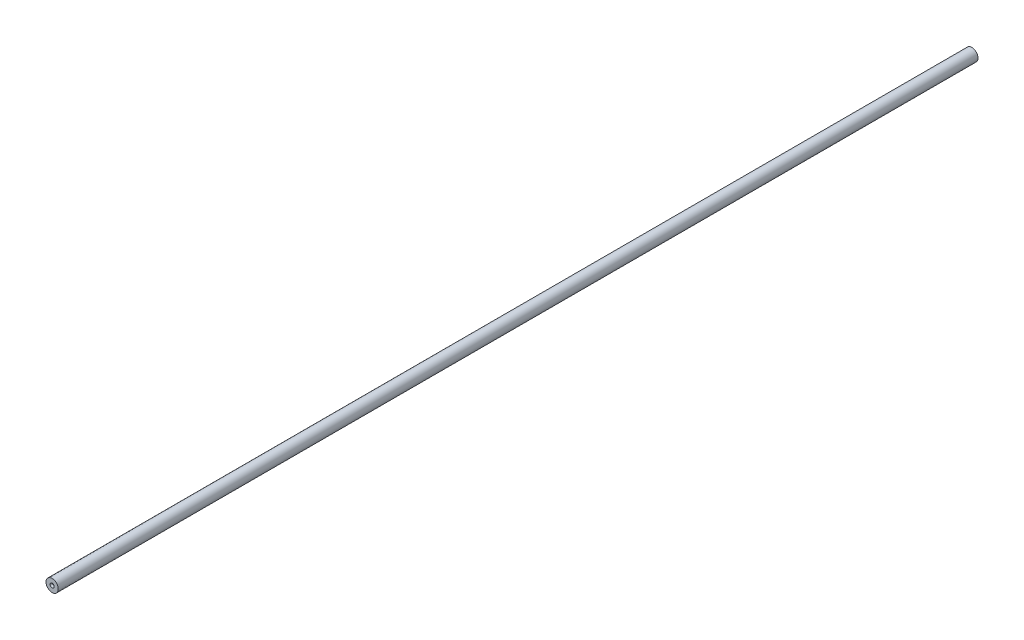
SolidWorks part; units mm, degrees
ref_plane "Front Plane" through (0, 0, 0) normal (0, 0, 1) x (1, 0, 0)
ref_plane "Top Plane" through (0, 0, 0) normal (0, 1, 0) x (1, 0, 0)
ref_plane "Right Plane" through (0, 0, 0) normal (1, 0, 0) x (0, 0, -1)
sketch "Sketch1" plane through (0, 0, 0) normal (0, 0, 1) x (1, 0, 0)
  circle A0 centre (0, 0) radius 8
  dimension "D1" = 16
extrude "Boss-Extrude1" add sketch "Sketch1" along normal mid plane 1200
cosmetic thread "Cosmetic Thread1" parameters "D2"=15
hole_wizard "CSK for M2.5 Flat Head Machine Screw1" positions "Sketch3" profile "Sketch4" countersink size "M2.5" standard "ANSI Metric"
sketch "Sketch3" plane through (0, 0, -600) normal (0, 0, -1) x (-1, 0, 0)
  point P0 (0, 0)
sketch "Sketch4" plane through (0, 0, -600) normal (1, 0, 0) x (0, 1, 0)
  line L0 (0, 0) -> (0, 5)
  line L1 (0, 5) -> (1.45, 4.1288)
  line L2 (1.45, 4.1288) -> (1.45, 2.2517)
  line L3 (1.45, 2.2517) -> (2.75, 0)
  line L5 (2.75, 0) -> (0, 0)
  line L6 (-1.45, 2.2517) -> (-2.75, 0) construction
  line L10 (0, 5) -> (-1.45, 4.1288) construction
  line L11 (0, -6.35) -> (0, 107.95) construction
  dimension "Hole Dia." = 2.9
  dimension "Hole Depth" = 5
  dimension "Near C'Sink Dia." = 5.5
  dimension "Near C'Sink Angle" = 60
  dimension "Drill Angle" = 118
mirror "Mirror1" about plane through (0, 0, 0) normal (0, 0, 1) of "CSK for M2.5 Flat Head Machine Screw1"
